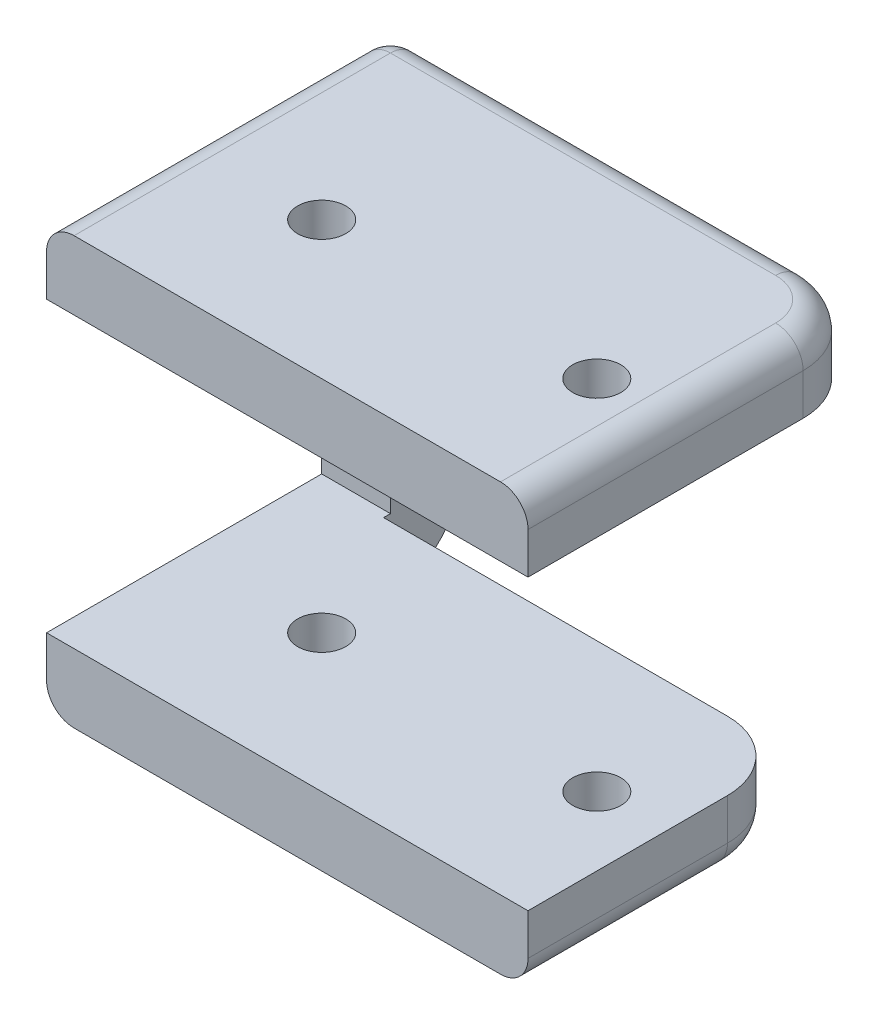
SolidWorks part; units mm, degrees
ref_plane "Front Plane" through (0, 0, 0) normal (0, 0, 1) x (1, 0, 0)
ref_plane "Top Plane" through (0, 0, 0) normal (0, 1, 0) x (1, 0, 0)
ref_plane "Right Plane" through (0, 0, 0) normal (1, 0, 0) x (0, 0, -1)
sketch "Sketch1" plane through (0, 0, 0) normal (0, 1, 0) x (1, 0, 0)
  line L0 (-15, 7.5) -> (15, 7.5) construction
  line L1 (-15, 12.5) -> (15, 12.5)
  line L2 (-15, 12.5) -> (-15, -12.5)
  line L3 (-15, -12.5) -> (15, -12.5)
  line L4 (15, 12.5) -> (15, -12.5)
  line L5 (-15, 12.5) -> (15, -12.5) construction
  line L6 (-15, -12.5) -> (15, 12.5) construction
  line L7 (-10, 7.5) -> (-10, -12.5) construction
  line L8 (10, 7.5) -> (10, -12.5) construction
  circle A0 centre (-10, -2.5) radius 1.75
  circle A1 centre (10, -2.5) radius 1.75
  point P0 (0, 0)
  dimension "D3" = 3.5
  dimension "D4" = 3.5
  dimension "D1" = 25
  dimension "D2" = 20
  dimension "D5" = 5
  dimension "D6" = 5
  dimension "D7" = 30
extrude "Boss-Extrude1" add sketch "Sketch1" along normal blind 5
sketch "Sketch2" plane through (-15, 0, 0) normal (-1, 0, 0) x (0, 0, 1)
  line L0 (12.5, 5) -> (12.5, 0) construction
  line L1 (-12.5, 5) -> (12.5, 5)
  line L2 (-12.5, 5) -> (-12.5, -26)
  line L3 (-12.5, -26) -> (12.5, -26)
  line L4 (12.5, 5) -> (12.5, 0)
  line L5 (-12.5, 0) -> (12.5, 0) construction
  line L6 (12.5, -21) -> (-7.5, -21)
  line L8 (12.5, 0) -> (-7.5, 0)
  line L9 (-7.5, -21) -> (-7.5, 0)
  line L10 (12.5, -21) -> (12.5, -26)
  point P11 (-7.5, 0)
  dimension "D1" = 31
  dimension "D2" = 20
  dimension "D3" = 21
extrude "Boss-Extrude2" add sketch "Sketch2" along normal blind 5
sketch "Sketch3" plane through (-15, 0, 0) normal (1, 0, 0) x (0, 0, -1)
  line L1 (-12.5, -26) -> (7, -26)
  line L2 (-12.5, -26) -> (-12.5, -21)
  line L3 (-12.5, -21) -> (7, -21)
  line L4 (7, -26) -> (7, -21)
  line L5 (7.5, -21) -> (7.5, 0) construction
  dimension "D1" = 0.5
extrude "Boss-Extrude3" add sketch "Sketch3" along normal blind 30
sketch "Sketch4" plane through (0, -26, 0) normal (0, -1, 0) x (1, 0, 0)
  circle A0 centre (-10, 2.5) radius 1.75
  circle A1 centre (10, 2.5) radius 1.75
  circle A2 centre (-10, 2.5) radius 1.75 construction
  circle A3 centre (10, 2.5) radius 1.75 construction
  point P6 (-12.5539, 4.2935)
  point P7 (-12.7685, 12.5)
  point P10 (-12.1066, -7.5)
  point P13 (-12.1782, -7.5)
  dimension "D1" = 3.5
  dimension "D2" = 3.5
extrude "Cut-Extrude1" cut sketch "Sketch4" against normal through all
fillet "Fillet1" radius 5 3 edges at (-17.5, -26, -12.5) (15, -23.5, -7) (15, 2.5, -12.5)
fillet "Fillet2" radius 2 10 edges at (15, -26, 5.25) (13.5355, -26, -5.5355) (-20, -26, 2.5) (-20, -24.5355, -11.0355) (-5, 5, -12.5) (13.5355, 5, -11.0355) (-2.5, -26, -7) (-20, -8, -12.5) (15, 5, 2.5) (-20, 5, 0)
